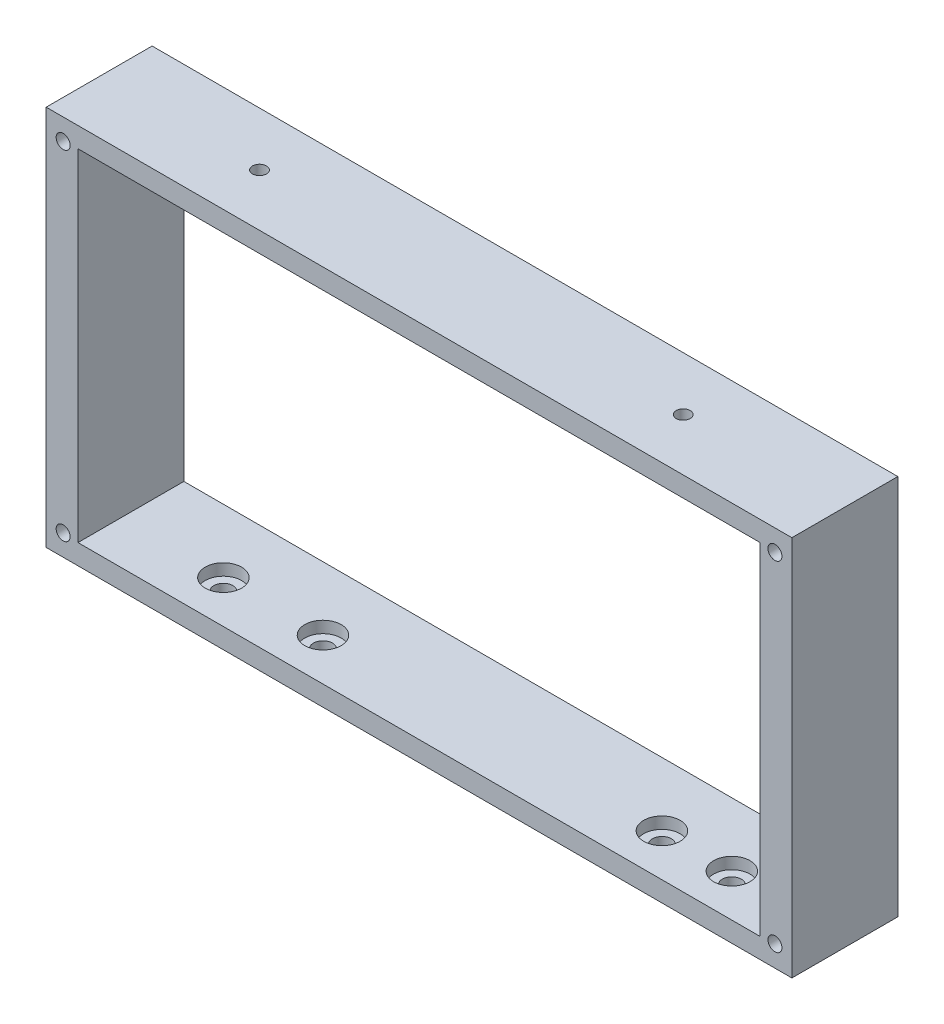
SolidWorks part; units mm, degrees
ref_plane "Front Plane" through (0, 0, 0) normal (0, 0, 1) x (1, 0, 0)
ref_plane "Top Plane" through (0, 0, 0) normal (0, 1, 0) x (1, 0, 0)
ref_plane "Right Plane" through (0, 0, 0) normal (1, 0, 0) x (0, 0, -1)
sketch "Sketch5" plane through (0, 0, 0) normal (0, 0, 1) x (1, 0, 0)
  line L1 (-80.5, -40.25) -> (80.5, -40.25)
  line L2 (-80.5, -40.25) -> (-80.5, 40.25)
  line L3 (-80.5, 40.25) -> (80.5, 40.25)
  line L4 (80.5, -40.25) -> (80.5, 40.25)
  line L5 (-80.5, -40.25) -> (80.5, 40.25) construction
  line L6 (-80.5, 40.25) -> (80.5, -40.25) construction
  line L7 (-88, -45) -> (88, -45)
  line L8 (-88, -45) -> (-88, 45)
  line L9 (-88, 45) -> (88, 45)
  line L10 (88, -45) -> (88, 45)
  line L11 (-88, -45) -> (88, 45) construction
  line L12 (-88, 45) -> (88, -45) construction
  point P0 (0, 0)
  point P6 (0, 0)
  dimension "D1" = 161
  dimension "D2" = 80.5
  dimension "D3" = 176
  dimension "D4" = 90
extrude "Boss-Extrude2" add sketch "Sketch5" along normal blind 25
hole_wizard "M4x0.7 Tapped Hole1" positions "Sketch6" profile "Sketch7" tap size "M4x0.7" standard "ANSI Metric" end condition through all
sketch "Sketch6" plane through (0, 0, 0) normal (0, 0, -1) x (-1, 0, 0)
  line L1 (-84, -40) -> (84, -40)
  line L2 (-84, -40) -> (-84, 40)
  line L3 (-84, 40) -> (84, 40)
  line L4 (84, -40) -> (84, 40)
  line L5 (-84, -40) -> (84, 40) construction
  line L6 (-84, 40) -> (84, -40) construction
  point P1 (0, 0)
  point P2 (84, 40)
  point P115 (-84, -40)
  point P116 (-84, 40)
  point P117 (84, -40)
  dimension "D1" = 168
  dimension "D2" = 80
sketch "Sketch7" plane through (0, 0, 0) normal (1, 0, 0) x (0, 1, 0)
  line L0 (0, 0) -> (0, 25)
  line L1 (0, 25) -> (1.65, 25)
  line L2 (1.65, 25) -> (1.65, 0)
  line L5 (1.65, 0) -> (0, 0)
  line L11 (0, -6.35) -> (0, 107.95) construction
  dimension "Thru Tap Drill Dia." = 3.3
  dimension "Thru Tap Drill Depth" = 25
cosmetic thread "Hole Thread1" parameters "D2"=4
cosmetic thread "Hole Thread2" parameters "D2"=4
cosmetic thread "Hole Thread3" parameters "D2"=4
cosmetic thread "Hole Thread4" parameters "D2"=4
hole_wizard "CBORE for M4 SBHCS1" positions "Sketch8" profile "Sketch10" counterbore size "M4" standard "ANSI Metric" end condition through all
sketch "Sketch8" plane through (0, -40.25, 0) normal (0, 1, 0) x (1, 0, 0)
  line L0 (-56.175, -15) -> (63.825, -15)
  line L2 (-88, -25) -> (88, -25) construction
  line L3 (-80.5, -25) -> (80.5, -25) construction
  line L4 (-32.675, -15) -> (47.325, -15)
  point P1 (-56.175, -15)
  point P2 (63.825, -15)
  point P11 (-32.675, -15)
  point P12 (47.325, -15)
  dimension "D1" = 120
  dimension "D2" = 10
  dimension "D3" = 10
  dimension "D4" = 31.825
  dimension "D5" = 80
  dimension "D6" = 23.5
sketch "Sketch10" plane through (-56.175, -40.25, 15) normal (1, 0, 0) x (0, 0, 1)
  line L0 (0, 0) -> (0, 4.75)
  line L1 (0, 4.75) -> (2.25, 4.75)
  line L3 (2.25, 4.75) -> (2.25, 2.75)
  line L4 (2.25, 2.75) -> (4.3, 2.75)
  line L5 (4.3, 2.75) -> (4.3, 0)
  line L7 (4.3, 0) -> (0, 0)
  line L11 (0, -6.35) -> (0, 107.95) construction
  dimension "Thru Hole Dia." = 4.5
  dimension "Thru Hole Depth" = 4.75
  dimension "C'Bore Dia." = 8.6
  dimension "C'Bore Depth" = 2.75
hole_wizard "M4x0.7 Tapped Hole2" positions "Sketch11" profile "Sketch12" tap size "M4x0.7" standard "ANSI Metric"
sketch "Sketch11" plane through (0, 0, 0) normal (0, 0, -1) x (-1, 0, 0)
  line L1 (-10, -42.5) -> (10, -42.5)
  line L2 (-10, -42.5) -> (-10, 42.5)
  line L3 (-10, 42.5) -> (10, 42.5)
  line L4 (10, -42.5) -> (10, 42.5)
  line L5 (-10, -42.5) -> (10, 42.5) construction
  line L6 (-10, 42.5) -> (10, -42.5) construction
  line L7 (-88, 45) -> (88, 45) construction
  point P0 (0, 0)
  point P1 (10, 42.5)
  point P48 (-10, -42.5)
  point P49 (-10, 42.5)
  point P50 (10, -42.5)
  dimension "D1" = 20
  dimension "D2" = 2.5
sketch "Sketch12" plane through (0, 0, 0) normal (1, 0, 0) x (0, 1, 0)
  line L0 (0, 0) -> (0, 5.9914)
  line L1 (0, 5.9914) -> (1.65, 5)
  line L2 (1.65, 5) -> (1.65, 0)
  line L5 (1.65, 0) -> (0, 0)
  line L10 (0, 5.9914) -> (-1.65, 5) construction
  line L11 (0, -6.35) -> (0, 107.95) construction
  dimension "Tap Drill Dia." = 3.3
  dimension "Tap Drill Depth" = 5
  dimension "Drill Angle" = 118
cosmetic thread "Hole Thread5" parameters "D1"=25, "D2"=4
cosmetic thread "Hole Thread6" parameters "D1"=25, "D2"=4
cosmetic thread "Hole Thread7" parameters "D1"=25, "D2"=4
cosmetic thread "Hole Thread8" parameters "D1"=25, "D2"=4
hole_wizard "M4x0.7 Tapped Hole3" positions "Sketch13" profile "Sketch14" tap size "M4x0.7" standard "ANSI Metric" end condition up to next
sketch "Sketch13" plane through (0, 45, 0) normal (0, 1, 0) x (1, 0, 0)
  line L0 (-50, -12.6553) -> (50, -12.6553)
  point P1 (-50, -12.6553)
  point P2 (50, -12.6553)
  point P5 (0, -12.6553)
  dimension "D1" = 100
sketch "Sketch14" plane through (-50, 45, 12.6553) normal (1, 0, 0) x (0, 0, 1)
  line L0 (0, 0) -> (0, 4.75)
  line L1 (0, 4.75) -> (1.65, 4.75)
  line L2 (1.65, 4.75) -> (1.65, 0)
  line L5 (1.65, 0) -> (0, 0)
  line L11 (0, -6.35) -> (0, 107.95) construction
  dimension "Thru Tap Drill Dia." = 3.3
  dimension "Thru Tap Drill Depth" = 4.75
cosmetic thread "Hole Thread9" parameters "D2"=4
cosmetic thread "Hole Thread10" parameters "D2"=4
